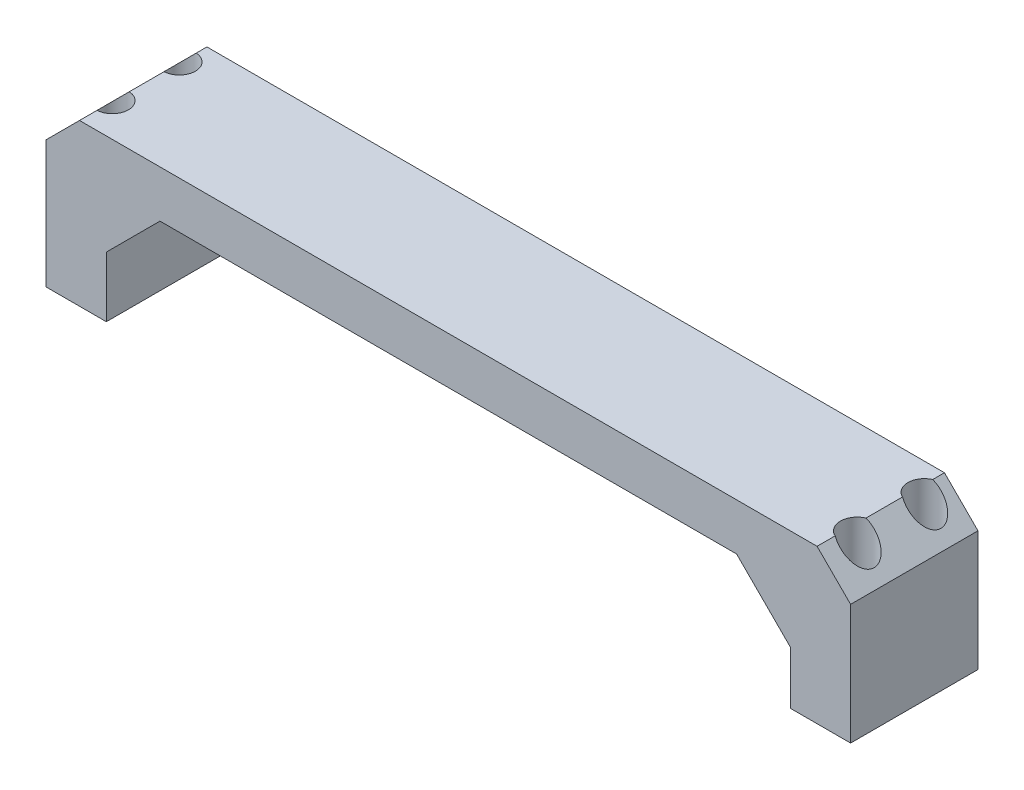
SolidWorks part; units mm, degrees
ref_plane "Front Plane" through (0, 0, 0) normal (0, 0, 1) x (1, 0, 0)
ref_plane "Top Plane" through (0, 0, 0) normal (0, 1, 0) x (1, 0, 0)
ref_plane "Right Plane" through (0, 0, 0) normal (1, 0, 0) x (0, 0, -1)
sketch "Sketch1" plane through (0, 0, 0) normal (0, 0, 1) x (1, 0, 0)
  line L0 (-71.0629, 12.7) -> (-71.0629, 0)
  line L1 (-71.0629, 12.7) -> (81.3371, 12.7)
  line L2 (-71.0629, 0) -> (81.3371, 0)
  line L3 (81.3371, 12.7) -> (81.3371, 0)
  line L4 (-71.0629, 0) -> (-59.6329, 0)
  line L5 (-71.0629, 0) -> (-71.0629, -17.78)
  line L6 (-59.6329, 0) -> (-59.6329, -17.78)
  line L7 (-71.0629, -17.78) -> (-59.6329, -17.78)
  line L8 (81.3371, 0) -> (69.9071, 0)
  line L9 (81.3371, 0) -> (81.3371, -16.4101)
  line L10 (69.9071, 0) -> (69.9071, -16.4101)
  line L11 (81.3371, -16.4101) -> (69.9071, -16.4101)
  dimension "D1" = 12.7
  dimension "D2" = 11.43
  dimension "D3" = 11.43
  dimension "D4" = 152.4
  dimension "D5" = 30.48
extrude "Boss-Extrude1" add sketch "Sketch1" along normal blind 13.97 and the other way blind 10.16 contours L5 L7 L6 L2 | L3 L1 L0 L2 | L11 L9 L2 L10 region at (5.1371, 6.35, 0) region at (-65.3479, -8.89, 0) region at (75.6221, -8.2051, 0)
chamfer "Chamfer1" distance 6.35 angle 45 4 edges at (69.9071, 0, 1.905) (-59.6329, 0, 1.905) (-71.0629, 12.7, 1.905) (81.3371, 12.7, 1.905)
sketch "Sketch2" plane through (0, -17.78, 0) normal (0, -1, 0) x (1, 0, 0)
  line L0 (0, 0) -> (0, 23.8529)
  circle A4 centre (-64.8653, 7.6052) radius 3.048
  circle A5 centre (-64.8653, -5.08) radius 3.048
  circle A8 centre (76.2571, 7.62) radius 3.1908
  circle A9 centre (76.2571, -5.08) radius 3.1257
  point P4 (0, 0)
  dimension "D1" = 6.096
  dimension "D2" = 6.096
extrude "Cut-Extrude1" cut sketch "Sketch2" against normal through all contours A4 | A5 | A8 | A9 region at (-64.8653, -17.78, 7.6052) region at (-64.8653, -17.78, -5.08) region at (76.2571, -17.78, 7.62) region at (76.2571, -17.78, -5.08)
chamfer "Chamfer2" distance 3.81 angle 45 2 edges at (5.1371, 0, -10.16) (5.1371, 0, 13.97)
